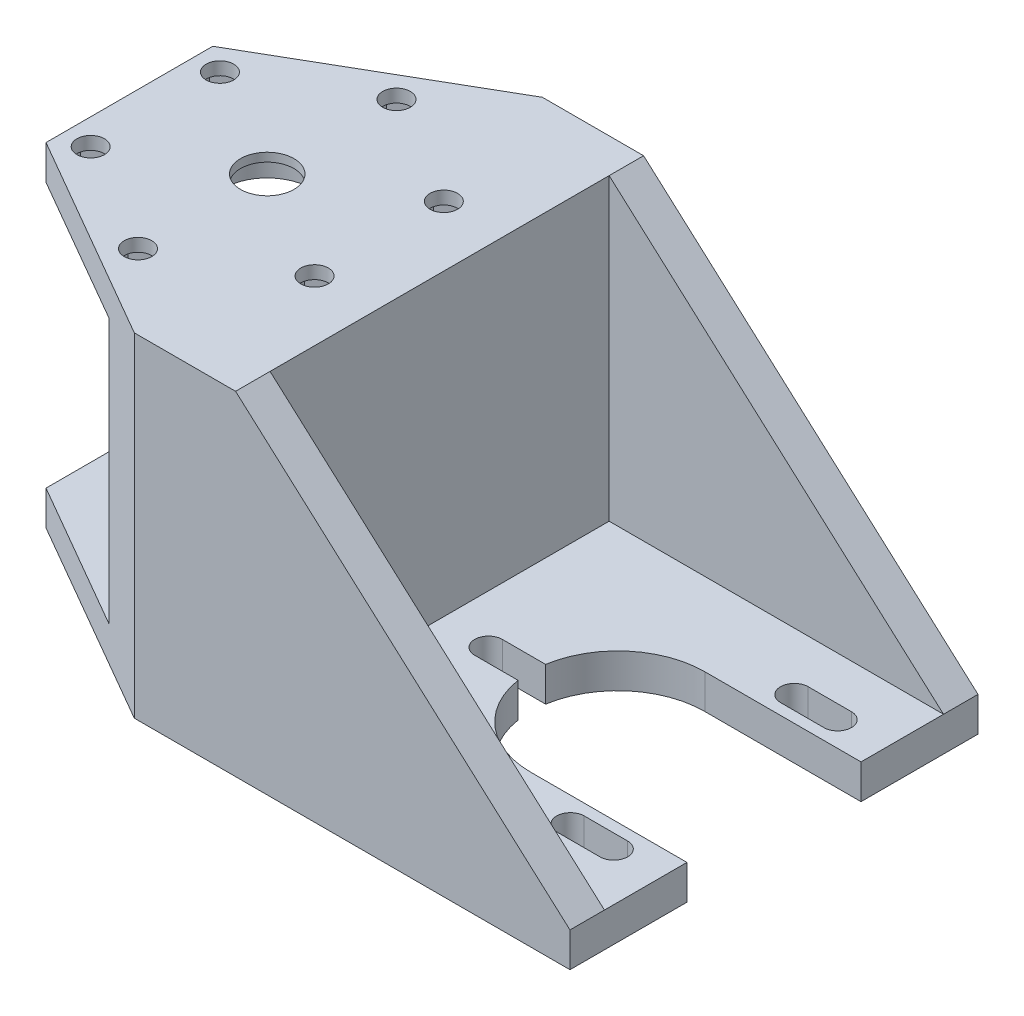
SolidWorks part; units mm, degrees
note: The reader was unsure of these and kept them because the rebuilt part matched: shared geometry of "Sketch3<4>", "Sketch3<5>", "Sketch3<6>".
ref_plane "Front Plane" through (0, 0, 0) normal (0, 0, 1) x (1, 0, 0)
ref_plane "Top Plane" through (0, 0, 0) normal (0, 1, 0) x (1, 0, 0)
ref_plane "Right Plane" through (0, 0, 0) normal (1, 0, 0) x (0, 0, -1)
sketch "Sketch1" plane through (0, 0, 0) normal (0, 0, 1) x (1, 0, 0)
  line L0 (-68.9432, 38.1067) -> (-32.9432, 38.1067)
  line L1 (-32.9432, 38.1067) -> (-32.9432, 3.3767)
  line L2 (-32.9432, 3.3767) -> (8.4068, 3.3767)
  line L3 (8.4068, 3.3767) -> (8.4068, -0.6233)
  line L4 (8.4068, -0.6233) -> (-68.9432, -0.6233)
  line L5 (-68.9432, -0.6233) -> (-68.9432, 3.3767)
  line L6 (-68.9432, 3.3767) -> (-36.9432, 3.3767)
  line L7 (-36.9432, 3.3767) -> (-36.9432, 34.1067)
  line L8 (-36.9432, 34.1067) -> (-68.9432, 34.1067)
  line L9 (-68.9432, 34.1067) -> (-68.9432, 38.1067)
  dimension "D2" = 4
  dimension "D1" = 4
  dimension "D3" = 4
  dimension "D4" = 41.35
  dimension "D5" = 32
  dimension "D6" = 30.73
extrude "Boss-Extrude1" add sketch "Sketch1" along normal blind 39.35
sketch "Sketch3" plane through (0, 3.3767, 0) normal (0, 1, 0) x (1, 0, 0)
  line L0 (-32.9432, -39.35) -> (8.4068, 0)
  line L1 (8.4068, -39.35) -> (8.4068, 0) construction
  line L2 (-36.9432, -39.35) -> (-68.9432, 0)
  line L3 (-12.2682, -19.675) -> (-27.2682, -19.675)
  line L4 (-12.2682, -29.775) -> (8.4068, -29.775)
  line L5 (-12.2682, -29.775) -> (-12.2682, -9.575)
  line L6 (-12.2682, -9.575) -> (8.4068, -9.575)
  line L7 (8.4068, -29.775) -> (8.4068, -9.575)
  line L8 (-60.5917, -20.925) -> (-45.2946, -20.925)
  line L9 (-60.5917, -20.925) -> (-60.5917, -18.425)
  line L10 (-60.5917, -18.425) -> (-45.2946, -18.425)
  line L11 (-45.2946, -20.925) -> (-45.2946, -18.425)
  line L12 (-12.2682, -19.675) -> (-4.7682, -32.6654)
  line L13 (-12.2682, -19.675) -> (-4.7682, -6.6846)
  line L14 (-52.9432, -19.675) -> (-52.9432, -34.675)
  line L15 (-27.2682, -21.275) -> (-22.2406, -21.275)
  line L16 (-27.2682, -21.275) -> (-27.2682, -18.075)
  line L17 (-27.2682, -18.075) -> (-22.2406, -18.075)
  line L18 (-22.2406, -21.275) -> (-22.2406, -18.075)
  line L19 (-4.7682, -34.2654) -> (0.2618, -34.2654)
  line L20 (-4.7682, -34.2654) -> (-4.7682, -31.0654)
  line L21 (-4.7682, -31.0654) -> (0.2618, -31.0654)
  line L22 (0.2618, -34.2654) -> (0.2618, -31.0654)
  line L23 (-4.7682, -5.0846) -> (0.2618, -5.0846)
  line L24 (-4.7682, -5.0846) -> (-4.7682, -8.2846)
  line L25 (-4.7682, -8.2846) -> (0.2618, -8.2846)
  line L26 (0.2618, -5.0846) -> (0.2618, -8.2846)
  line L27 (-52.9432, -19.675) -> (-39.9528, -12.175)
  line L28 (-52.9432, -19.675) -> (-65.9336, -12.175)
  line L29 (-52.9432, -19.675) -> (-52.9432, -4.675)
  line L30 (-52.9432, -19.675) -> (-39.9528, -27.175)
  line L31 (-52.9432, -19.675) -> (-65.9336, -27.175)
  circle A0 centre (-12.2682, -19.675) radius 3.1
  circle A1 centre (-52.9432, -19.675) radius 3.1
  circle A2 centre (-52.9432, -19.675) radius 5.1
  circle A3 centre (-12.2682, -19.675) radius 10.1
  circle A4 centre (-52.9432, -19.675) radius 7.75
  circle A5 centre (-52.9432, -19.675) radius 5.5
  circle A6 centre (-12.2682, -19.675) radius 15
  circle A7 centre (-12.2682, -19.675) radius 14
  circle A8 centre (-4.7682, -32.6654) radius 1.6
  circle A9 centre (-4.7682, -6.6846) radius 1.6
  circle A10 centre (-27.2682, -19.675) radius 1.6
  circle A11 centre (0.2618, -32.6654) radius 1.6
  circle A12 centre (0.2618, -6.6846) radius 1.6
  circle A13 centre (-52.9432, -19.675) radius 15
  circle A14 centre (-52.9432, -34.675) radius 1.6
  circle A15 centre (-65.9336, -27.175) radius 1.6
  circle A16 centre (-65.9336, -12.175) radius 1.6
  circle A17 centre (-52.9432, -4.675) radius 1.6
  circle A18 centre (-39.9528, -12.175) radius 1.6
  circle A19 centre (-39.9528, -27.175) radius 1.6
  point P5 (-12.2682, -29.775)
  point P12 (8.4068, -19.675)
  point P18 (-12.2682, -9.575)
  point P24 (-60.6932, -19.675)
  point P30 (-60.5917, -19.675)
  dimension "D1" = 6.2
  dimension "D2" = 6.2
  dimension "D3" = 10.2
  dimension "D4" = 20.2
  dimension "D6" = 15.5
  dimension "D7" = 11
  dimension "D8" = 28
  dimension "D9" = 30
  dimension "D12" = 3.2
  dimension "D13" = 3.2
  dimension "D14" = 3.2
  dimension "D17" = 30
  dimension "D22" = 3.2
  dimension "D5" = 2.5
  dimension "D10" = 120
  dimension "D11" = 120
  dimension "D15" = 40.675
  dimension "D16" = 5.03
  dimension "D18" = 120
  dimension "D19" = 120
  dimension "D20" = 120
  dimension "D21" = 120
extrude "Cut-Extrude2" cut sketch "Sketch3" against normal blind 3 and the other way offset from surface (33.73 mm away) 3 contours A2 other way up to face at (-52.9432, 34.1067, 19.675)
extrude "Cut-Extrude3" cut sketch "Sketch3<4>" along normal offset from surface (33.73 mm away) 3 contours A5 L8 L11 L10 | A5 L10 L9 L8 up to face at (-58.0432, 34.1067, 19.675) offset beyond the face yes
sketch "Sketch3<4>" plane through (0, 3.3767, 0) normal (0, 1, 0) x (1, 0, 0) same geometry as "Sketch3"
extrude "Cut-Extrude4" cut sketch "Sketch3<5>" against normal through all both and the other way through all contours L4 L7 L6 L5 | A3 | A1 | A8 | L19 L22 L21 L20 | A11 | L23 L26 L25 L24 | A9 | A12 | A10 | L17 L18 L15 L16
sketch "Sketch3<5>" plane through (0, 3.3767, 0) normal (0, 1, 0) x (1, 0, 0) same geometry as "Sketch3"
extrude "Cut-Extrude5" cut sketch "Sketch3<6>" along normal through all contours A14 | A15 | A16 | A17 | A18 | A19
sketch "Sketch3<6>" plane through (0, 3.3767, 0) normal (0, 1, 0) x (1, 0, 0) same geometry as "Sketch3"
sketch "Sketch4" plane through (0, 0, 39.35) normal (0, 0, 1) x (1, 0, 0)
  line L1 (-68.9432, 38.1067) -> (8.4068, 38.1067)
  line L2 (-68.9432, 38.1067) -> (-68.9432, -0.6233)
  line L3 (-68.9432, -0.6233) -> (8.4068, -0.6233)
  line L4 (8.4068, 38.1067) -> (8.4068, -0.6233)
extrude "Boss-Extrude2" add sketch "Sketch4" along normal blind 4
sketch "Sketch5" plane through (0, 0, 0) normal (0, 0, -1) x (-1, 0, 0)
  line L1 (68.9432, 38.1067) -> (-8.4068, 38.1067)
  line L2 (68.9432, 38.1067) -> (68.9432, -0.6233)
  line L3 (68.9432, -0.6233) -> (-8.4068, -0.6233)
  line L4 (-8.4068, 38.1067) -> (-8.4068, -0.6233)
  dimension "D1" = 38.73
extrude "Boss-Extrude3" add sketch "Sketch5" along normal blind 4
sketch "Sketch6" plane through (0, 0, 43.35) normal (0, 0, 1) x (1, 0, 0)
  line L0 (-32.9432, 38.1067) -> (5.8618, 3.3767)
  line L1 (8.4068, 3.3767) -> (-32.9432, 3.3767) construction
  line L2 (5.8618, 3.3767) -> (5.8618, -0.6233)
  line L3 (-68.9432, -0.6233) -> (8.4068, -0.6233) construction
  line L4 (5.8618, -0.6233) -> (8.4068, -0.6233)
  line L5 (8.4068, -0.6233) -> (8.4068, 38.1067)
  line L6 (8.4068, 38.1067) -> (-32.9432, 38.1067)
  line L7 (1.8618, -0.6233) -> (1.8618, 3.3767) construction
  dimension "D1" = 4
extrude "Cut-Extrude6" cut sketch "Sketch6" against normal through all both and the other way through all
sketch "Sketch8" plane through (0, 34.1067, 0) normal (0, -1, 0) x (1, 0, 0)
  line L1 (-65.9336, 15.4082) -> (-68.7336, 13.7916)
  line L2 (-68.7336, 13.7916) -> (-68.7336, 10.5584)
  line L3 (-68.7336, 10.5584) -> (-65.9336, 8.9418)
  line L4 (-65.9336, 8.9418) -> (-63.1336, 10.5584)
  line L5 (-63.1336, 10.5584) -> (-63.1336, 13.7916)
  line L6 (-63.1336, 13.7916) -> (-65.9336, 15.4082)
  line L7 (-65.9336, 30.4082) -> (-68.7336, 28.7916)
  line L8 (-68.7336, 28.7916) -> (-68.7336, 25.5584)
  line L9 (-68.7336, 25.5584) -> (-65.9336, 23.9418)
  line L10 (-65.9336, 23.9418) -> (-63.1336, 25.5584)
  line L11 (-63.1336, 25.5584) -> (-63.1336, 28.7916)
  line L12 (-63.1336, 28.7916) -> (-65.9336, 30.4082)
  line L13 (-52.9432, 1.4418) -> (-50.1432, 3.0584)
  line L14 (-50.1432, 3.0584) -> (-50.1432, 6.2916)
  line L15 (-50.1432, 6.2916) -> (-52.9432, 7.9082)
  line L16 (-52.9432, 7.9082) -> (-55.7432, 6.2916)
  line L17 (-55.7432, 6.2916) -> (-55.7432, 3.0584)
  line L18 (-55.7432, 3.0584) -> (-52.9432, 1.4418)
  line L19 (-39.9528, 8.9418) -> (-37.1528, 10.5584)
  line L20 (-37.1528, 10.5584) -> (-37.1528, 13.7916)
  line L21 (-37.1528, 13.7916) -> (-39.9528, 15.4082)
  line L22 (-39.9528, 15.4082) -> (-42.7528, 13.7916)
  line L23 (-42.7528, 13.7916) -> (-42.7528, 10.5584)
  line L24 (-42.7528, 10.5584) -> (-39.9528, 8.9418)
  line L25 (-39.9528, 23.9418) -> (-37.1528, 25.5584)
  line L26 (-37.1528, 25.5584) -> (-37.1528, 28.7916)
  line L27 (-37.1528, 28.7916) -> (-39.9528, 30.4082)
  line L28 (-39.9528, 30.4082) -> (-42.7528, 28.7916)
  line L29 (-42.7528, 28.7916) -> (-42.7528, 25.5584)
  line L30 (-42.7528, 25.5584) -> (-39.9528, 23.9418)
  line L31 (-52.9432, 37.9082) -> (-55.7432, 36.2916)
  line L32 (-55.7432, 36.2916) -> (-55.7432, 33.0584)
  line L33 (-55.7432, 33.0584) -> (-52.9432, 31.4418)
  line L34 (-52.9432, 31.4418) -> (-50.1432, 33.0584)
  line L35 (-50.1432, 33.0584) -> (-50.1432, 36.2916)
  line L36 (-50.1432, 36.2916) -> (-52.9432, 37.9082)
  circle A0 centre (-65.9336, 12.175) radius 2.8 construction
  circle A1 centre (-65.9336, 27.175) radius 2.8 construction
  circle A2 centre (-52.9432, 4.675) radius 2.8 construction
  circle A3 centre (-39.9528, 12.175) radius 2.8 construction
  circle A4 centre (-39.9528, 27.175) radius 2.8 construction
  circle A5 centre (-52.9432, 34.675) radius 2.8 construction
  dimension "D1" = 5.6
extrude "Cut-Extrude7" cut sketch "Sketch8" against normal offset from surface (2.5 mm away) 1.5 up to face at (-52.9432, 38.1067, 36.275)
chamfer "Chamfer1" distance 14 angle 60 2 edges at (-68.9432, 18.7417, 43.35) (-68.9432, 18.7417, -4)
equation "\"h_thickness\"=4"
equation "\"D2@Sketch1\"=\"h_thickness\""
equation "\"v_thickness\"=4"
equation "\"D3@Sketch1\"=\"v_thickness\""
equation "\"enc_od\"=38.35"
equation "\"D4@Sketch1\"=\"enc_od\"+3"
equation "\"shaft_clearance\"=32"
equation "\"D5@Sketch1\"=\"shaft_clearance\""
equation "\"D1@Sketch1\"=\"h_thickness\""
equation "\"tok_height\"=17.2"
equation "\"D6@Sketch1\"=\"tok_height\"+\"pin_collar_height\"-2.8+1"
equation "\"D1@Boss-Extrude1\"=\"enc_od\"+1"
equation "\"shaft_dia\"=6.2"
equation "\"D1@Sketch3\"=\"shaft_dia\""
equation "\"D2@Sketch3\"=\"shaft_dia\""
equation "\"bearing_od\"=10.2"
equation "\"D3@Sketch3\"=\"bearing_od\""
equation "\"enc_collar_dia\"=20.9592"
equation "\"tok_pin_od\"=15.5"
equation "\"D6@Sketch3\"=\"tok_pin_od\""
equation "\"tok_pin_id\"=11"
equation "\"D7@Sketch3\"=\"tok_pin_id\""
equation "\"enc_mounting_28\"=28"
equation "\"D8@Sketch3\"=\"enc_mounting_28\""
equation "\"enc_mount_30\"=30"
equation "\"m3_hole\"=3.2"
equation "\"D14@Sketch3\"=\"m3_hole\""
equation "\"D13@Sketch3\"=\"m3_hole\""
equation "\"D12@Sketch3\"=\"m3_hole\""
equation "\"enc_slide\"=5.03"
equation "\"D16@Sketch3\"=\"enc_slide\""
equation "\"pin_collar_height\"= 15.33"
equation "\"D17@Sketch3\"=\"enc_mount_30\""
equation "\"D9@Sketch3\"=\"enc_mount_30\""
equation "\"D22@Sketch3\"=\"m3_hole\""
equation "\"side_wall_thickness\"=4"
equation "\"D1@Boss-Extrude2\"=\"side_wall_thickness\""
equation "\"D1@Boss-Extrude3\"=\"side_wall_thickness\""
equation "\"m3_nut_hole\"=5.6"
equation "\"D1@Sketch8\"=\"m3_nut_hole\""
equation "\"chamfer_dist\"=14"
equation "\"D1@Chamfer1\"=\"chamfer_dist\""
